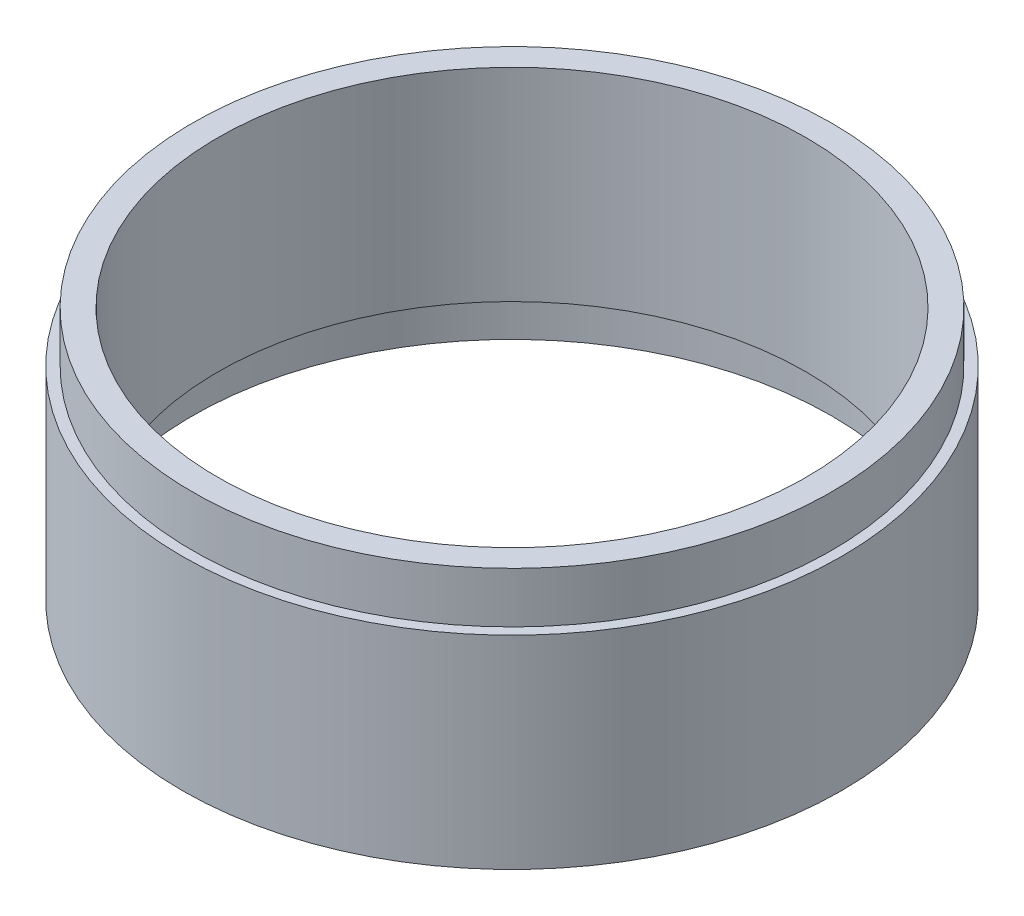
SolidWorks part; units mm, degrees
material "HYPALON"
ref_plane "Front Plane" through (0, 0, 0) normal (0, 0, 1) x (1, 0, 0)
ref_plane "Top Plane" through (0, 0, 0) normal (0, 1, 0) x (1, 0, 0)
ref_plane "Right Plane" through (0, 0, 0) normal (1, 0, 0) x (0, 0, -1)
sketch "Szkic1" plane through (0, 0, 0) normal (0, 0, 1) x (1, 0, 0)
  line L0 (0, 0) -> (-65, 0)
  line L1 (-65, 0) -> (-65, 10)
  line L2 (-63, 10) -> (-58, 10)
  line L3 (-58, 10) -> (-58, 50)
  line L4 (-63, 10) -> (-63, 0)
  line L5 (-58, 50) -> (-63, 50)
  line L7 (-65, 10) -> (-65, 40)
  line L8 (-65, 40) -> (-63, 40)
  line L9 (-63, 40) -> (-63, 50)
  line L13 (0, 0) -> (0, 22.4148)
  dimension "D1" = 65
  dimension "D2" = 10
  dimension "D3" = 7
  dimension "D4" = 50
  dimension "D5" = 2
  dimension "D7" = 2
  dimension "D8" = 10
revolve "Obrót1" add sketch "Szkic1" angle 360 about L13 region at (-61.5, 27.1429, 0)
